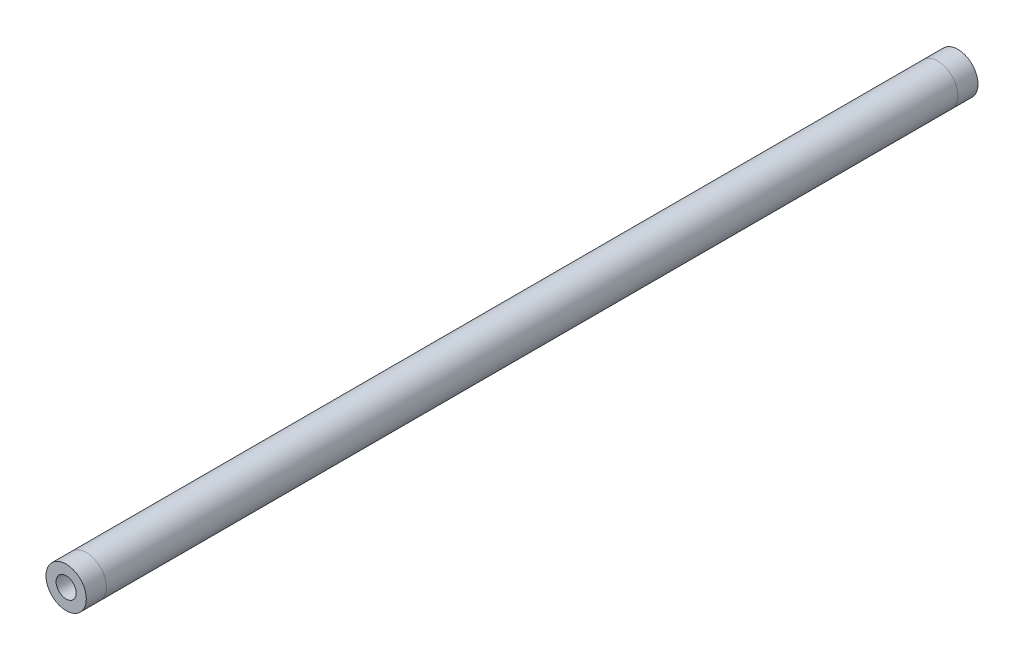
SolidWorks part; units mm, degrees
ref_plane "Front Plane" through (0, 0, 0) normal (0, 0, 1) x (1, 0, 0)
ref_plane "Top Plane" through (0, 0, 0) normal (0, 1, 0) x (1, 0, 0)
ref_plane "Right Plane" through (0, 0, 0) normal (1, 0, 0) x (0, 0, -1)
sketch "Axis" plane through (0, 0, 0) normal (1, 0, 0) x (0, 0, -1)
  line L0 (0, 0) -> (280.6999, 0) construction
  line L1 (280.6999, 0) -> (274.3499, 0)
  line L2 (280.6999, 0) -> (302.5947, 0) construction
  line L3 (0, 0) -> (-21.8948, 0) construction
  point P4 (0, 0)
  point P5 (280.6999, 0)
  point P6 (274.3499, 0)
  dimension "D1" = 6.35
  dimension "D2" = 21.8948
  dimension "D3" = 21.8948
sketch "Sketch1" plane through (0, 0, 0) normal (0, 0, 1) x (1, 0, 0)
  circle A0 centre (0, 0) radius 6.35
  circle A1 centre (0, 0) radius 4.826
  circle A2 centre (0, 0) radius 3.175
  dimension "D1" = 12.7
  dimension "D2" = 1.524
  dimension "D3" = 6.35
extrude "Threaded insert 1-1" add sketch "Sketch1" against normal blind 6.35 contours A0 A1 | A1 A2 region at (-6.1704, 0, 0) region at (-4.6895, 0, 0)
extrude "Threaded insert 1-2" add sketch "Sketch1<3>" against normal blind 9.525 from surface contours A1 A2 region at (-4.6895, 0, 0) starting at face at (6.35, 0, -6.35)
sketch "Sketch1<3>" plane through (0, 0, 0) normal (0, 0, 1) x (1, 0, 0) same geometry as "Sketch1"
extrude "Tube extrude" add sketch "Sketch1<4>" against normal up to vertex (274.3499 mm away) from surface separate body contours A0 A1 region at (-6.1704, 0, 0) up to point (0, 0, -274.3499) starting at face at (4.826, 0, -6.35)
sketch "Sketch1<4>" plane through (0, 0, 0) normal (0, 0, 1) x (1, 0, 0) same geometry as "Sketch1"
extrude "Threaded insert 2-1" add sketch "Sketch1<6>" along normal blind 9.525 from surface separate body contours A1 A2 region at (-4.6895, 0, 0) starting at face at (4.826, 0, -274.3499)
sketch "Sketch1<6>" plane through (0, 0, 0) normal (0, 0, 1) x (1, 0, 0) same geometry as "Sketch1"
extrude "Threaded insert 2-2" add sketch "Sketch1<9>" against normal blind 6.35 from surface separate body contours A1 A2 | A0 A1 region at (-6.1704, 0, 0) region at (-4.6895, 0, 0) starting at face at (4.826, 0, -274.3499)
sketch "Sketch1<9>" plane through (0, 0, 0) normal (0, 0, 1) x (1, 0, 0) same geometry as "Sketch1"
combine bodies "Combine1" operation type add bodies to combine 106 104
equation "\"Threaded insert outer thickness\"= .25"
equation "\"D1@Threaded insert 1-1\"=\"Threaded insert outer thickness\""
equation "\"D1@Threaded insert 2-2\"=\"Threaded insert outer thickness\""
equation "\"D1@Axis\" = \"Threaded insert outer thickness\""
